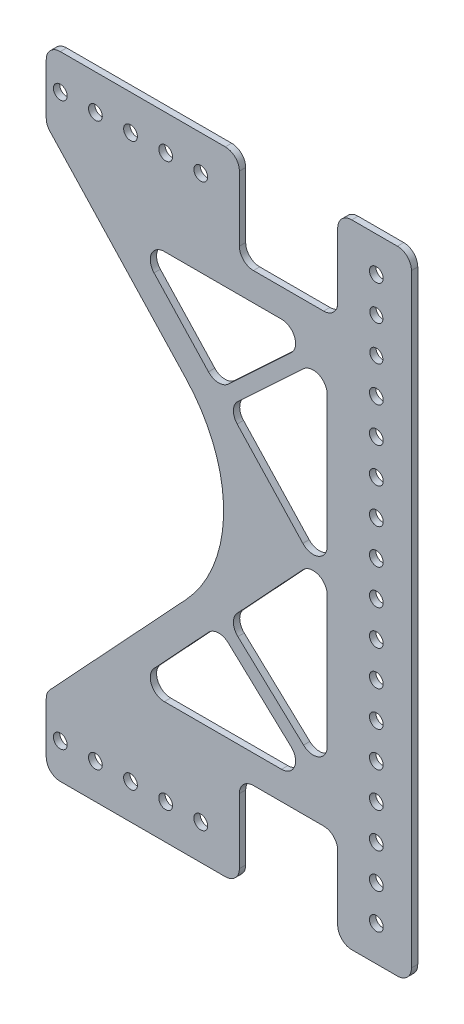
SolidWorks part; units mm, degrees
ref_plane "Front Plane" through (0, 0, 0) normal (0, 0, 1) x (1, 0, 0)
ref_plane "Top Plane" through (0, 0, 0) normal (0, 1, 0) x (1, 0, 0)
ref_plane "Right Plane" through (0, 0, 0) normal (1, 0, 0) x (0, 0, -1)
sketch "Sketch1" plane through (0, 0, 0) normal (0, 0, 1) x (1, 0, 0)
  line L11 (65.4076, 898.4977) -> (48.8976, 898.4977)
  line L12 (43.8176, 893.4177) -> (43.8176, 869.9227)
  line L13 (38.7376, 864.8427) -> (13.3376, 864.8427)
  line L14 (8.2576, 869.9227) -> (8.2576, 893.4177)
  line L15 (3.1776, 898.4977) -> (-56.5124, 898.4977)
  line L16 (-60.2304, 871.6349) -> (-11.0513, 818.8143)
  line L17 (70.4876, 893.4177) -> (70.4876, 784.1977)
  line L18 (-61.5924, 875.0965) -> (-61.5924, 893.4177)
  line L20 (-22.6122, 846.1411) -> (-2.9253, 824.9965)
  line L21 (40.0076, 791.7957) -> (40.0076, 839.4169)
  line L22 (23.5028, 854.6827) -> (-18.8942, 854.6827)
  line L23 (70.4876, 674.9777) -> (70.4876, 784.1977)
  line L24 (65.4076, 669.8977) -> (48.8976, 669.8977)
  line L25 (43.8176, 674.9777) -> (43.8176, 698.4727)
  line L26 (38.7376, 703.5527) -> (13.3376, 703.5527)
  line L27 (8.2576, 698.4727) -> (8.2576, 674.9777)
  line L28 (-60.2304, 696.7606) -> (-11.0513, 749.5812)
  line L29 (3.1776, 669.8977) -> (-56.5124, 669.8977)
  line L30 (-61.5924, 693.2989) -> (-61.5924, 674.9777)
  line L31 (26.9645, 845.8848) -> (4.2543, 824.7402)
  line L32 (7.4596, 754.5529) -> (31.2096, 780.0614)
  line L33 (31.4659, 843.1349) -> (7.716, 821.0222)
  line L34 (7.4596, 813.8426) -> (31.2096, 788.3341)
  line L35 (40.0076, 776.5997) -> (40.0076, 728.9785)
  line L36 (31.4659, 725.2606) -> (7.716, 747.3732)
  line L37 (26.9645, 722.5107) -> (4.2543, 743.6552)
  line L38 (-22.6122, 722.2544) -> (-2.9253, 743.3989)
  line L39 (23.5028, 713.7127) -> (-18.8942, 713.7127)
  arc A1 (65.4076, 898.4977) -> (70.4876, 893.4177) centre (65.4076, 893.4177) cw
  arc A2 (48.8976, 898.4977) -> (43.8176, 893.4177) centre (48.8976, 893.4177) ccw
  arc A3 (43.8176, 869.9227) -> (38.7376, 864.8427) centre (38.7376, 869.9227) cw
  arc A4 (13.3376, 864.8427) -> (8.2576, 869.9227) centre (13.3376, 869.9227) cw
  arc A5 (8.2576, 893.4177) -> (3.1776, 898.4977) centre (3.1776, 893.4177) ccw
  arc A6 (-56.5124, 898.4977) -> (-61.5924, 893.4177) centre (-56.5124, 893.4177) ccw
  circle A7 centre (-31.1124, 885.7977) radius 2.4892
  circle A8 centre (-18.4124, 885.7977) radius 2.4892
  circle A9 centre (-5.7124, 885.7977) radius 2.4892
  circle A11 centre (57.7876, 860.3977) radius 2.3719
  circle A12 centre (57.7876, 847.6977) radius 2.4892
  circle A13 centre (57.7876, 834.9977) radius 2.4892
  circle A14 centre (57.7876, 822.2977) radius 2.4892
  circle A15 centre (57.7876, 809.5977) radius 2.4892
  arc A16 (-60.2304, 871.6349) -> (-61.5924, 875.0965) centre (-56.5124, 875.0965) cw
  arc A17 (31.2096, 788.3341) -> (40.0076, 791.7957) centre (34.9276, 791.7957) ccw
  arc A18 (-22.6122, 846.1411) -> (-18.8942, 854.6827) centre (-18.8942, 849.6027) cw
  arc A19 (65.4076, 669.8977) -> (70.4876, 674.9777) centre (65.4076, 674.9777) ccw
  arc A20 (48.8976, 669.8977) -> (43.8176, 674.9777) centre (48.8976, 674.9777) cw
  arc A21 (43.8176, 698.4727) -> (38.7376, 703.5527) centre (38.7376, 698.4727) ccw
  arc A22 (13.3376, 703.5527) -> (8.2576, 698.4727) centre (13.3376, 698.4727) ccw
  arc A23 (8.2576, 674.9777) -> (3.1776, 669.8977) centre (3.1776, 674.9777) cw
  circle A24 centre (-5.7124, 682.5977) radius 2.4892
  circle A25 centre (-18.4124, 682.5977) radius 2.4892
  circle A26 centre (-31.1124, 682.5977) radius 2.4892
  arc A27 (-60.2304, 696.7606) -> (-61.5924, 693.2989) centre (-56.5124, 693.2989) ccw
  arc A28 (-56.5124, 669.8977) -> (-61.5924, 674.9777) centre (-56.5124, 674.9777) cw
  circle A29 centre (57.7876, 733.3977) radius 2.4892
  circle A30 centre (57.7876, 720.6977) radius 2.4892
  circle A31 centre (57.7876, 707.9977) radius 2.4892
  circle A32 centre (57.7876, 682.5977) radius 2.4892
  circle A33 centre (57.7876, 885.7977) radius 2.4892
  arc A34 (-11.0513, 818.8143) -> (-11.0513, 749.5812) centre (-48.231, 784.1977) cw
  circle A35 centre (57.7876, 771.4977) radius 2.4892
  circle A36 centre (57.7876, 758.7977) radius 2.4892
  circle A37 centre (57.7876, 746.0977) radius 2.4892
  circle A38 centre (-56.5124, 885.7977) radius 2.4892
  circle A39 centre (-43.8124, 885.7977) radius 2.4892
  circle A40 centre (-43.8124, 682.5977) radius 2.4892
  circle A41 centre (-56.5124, 682.5977) radius 2.4892
  arc A42 (7.716, 821.0222) -> (7.4596, 813.8426) centre (11.1776, 817.3043) ccw
  arc A43 (31.4659, 843.1349) -> (40.0076, 839.4169) centre (34.9276, 839.4169) cw
  arc A44 (26.9645, 845.8848) -> (23.5028, 854.6827) centre (23.5028, 849.6027) ccw
  arc A45 (4.2543, 824.7402) -> (-2.9253, 824.9965) centre (0.7927, 828.4582) cw
  arc A46 (31.2096, 780.0614) -> (40.0076, 776.5997) centre (34.9276, 776.5997) cw
  arc A47 (7.716, 747.3732) -> (7.4596, 754.5529) centre (11.1776, 751.0912) cw
  arc A48 (31.4659, 725.2606) -> (40.0076, 728.9785) centre (34.9276, 728.9785) ccw
  arc A49 (26.9645, 722.5107) -> (23.5028, 713.7127) centre (23.5028, 718.7927) cw
  arc A50 (4.2543, 743.6552) -> (-2.9253, 743.3989) centre (0.7927, 739.9373) ccw
  arc A51 (-22.6122, 722.2544) -> (-18.8942, 713.7127) centre (-18.8942, 718.7927) ccw
  circle A52 centre (57.7876, 796.8977) radius 2.4892
  circle A53 centre (57.7876, 784.1977) radius 2.4892
  circle A54 centre (57.7876, 873.0977) radius 2.3719
  circle A55 centre (57.7876, 695.2977) radius 2.4892
  point P14 (70.4876, 784.1977)
  point P17 (45.0876, 784.1977)
  dimension "D1" = 10.16
  dimension "D3" = 5.08
  dimension "D4" = 50.8
  dimension "D5" = 5.08
  dimension "D6" = 5.08
  dimension "D8" = 5.08
  dimension "D11" = 12.7
  dimension "D12" = 12.7
  dimension "D2" = 10.16
  dimension "D7" = 5.08
  dimension "D9" = 3
  dimension "D10" = 2
extrude "Boss-Extrude2" add sketch "Sketch1" along normal blind 2.286 contours L16 A34 L28 A27 L30 A28 L29 A23 L27 A22 L26 A21 L25 A20 L24 A19 L23 L17 A1 L11 A2 L12 A3 L13 A4 L14 A5 L15 A6 L18 A16 A55 A54 A53 A52 A51 L38 A50 L37 A49 L39 A48 L36 A47 L32 region at (15.2139, 784.2164, 0)
sketch "Sketch2" [suppressed] plane through (0, 0, 0) normal (0, 0, -1) x (-1, 0, 0)
  line L0 (-70.4876, 784.1977) -> (29.7113, 784.1977) construction
  line L1 (-70.4876, 674.9777) -> (-70.4876, 893.4177) construction
  circle A0 centre (-26.4815, 826.617) radius 2.54
  circle A1 centre (-30.3527, 804.0119) radius 2.54
  circle A2 centre (-12.2581, 845.8816) radius 2.54
  circle A3 centre (5.9262, 840.3002) radius 2.54
  circle A4 centre (5.9262, 728.0952) radius 2.54
  circle A5 centre (-12.2581, 722.5139) radius 2.54
  circle A6 centre (-30.3527, 764.3835) radius 2.54
  circle A7 centre (-26.4815, 741.7785) radius 2.54
  dimension "D1" = 5.08
sketch "Sketch3" plane through (0, 0, 2.286) normal (0, 0, 1) x (1, 0, 0)
  line L0 (70.4876, -316.1874) -> (70.4876, 49683.8126) construction
  line L1 (-960.1876, 669.8977) -> (49039.8124, 669.8977) construction
  line L2 (70.4876, 674.9777) -> (70.4876, 893.4177) construction
  line L3 (65.4076, 669.8977) -> (48.8976, 669.8977) construction
  point P3 (70.4876, 669.8977)
